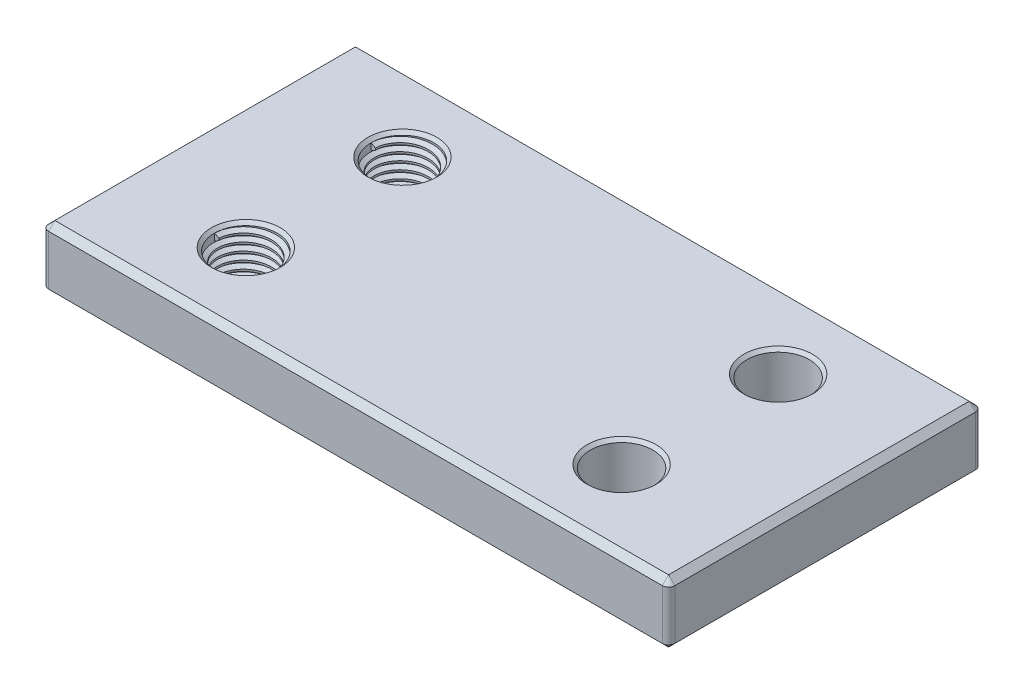
SolidWorks part; units mm, degrees
ref_plane "Alzado" through (0, 0, 0) normal (0, 0, 1) x (1, 0, 0)
ref_plane "Planta" through (0, 0, 0) normal (0, 1, 0) x (1, 0, 0)
ref_plane "Vista lateral" through (0, 0, 0) normal (1, 0, 0) x (0, 0, -1)
sketch "Croquis1" plane through (0, 0, 0) normal (0, 1, 0) x (1, 0, 0)
  line L0 (0, -1) -> (0, -49)
  line L1 (-1, -50) -> (-99, -50)
  line L2 (-100, -49) -> (-100, -1)
  line L3 (-99, 0) -> (-1, 0)
  arc A0 (0, -1) -> (-1, 0) centre (-1, -1) ccw
  arc A1 (0, -49) -> (-1, -50) centre (-1, -49) cw
  arc A2 (-99, -50) -> (-100, -49) centre (-99, -49) cw
  arc A3 (-100, -1) -> (-99, 0) centre (-99, -1) cw
  point P7 (0, 0)
  point P10 (0, -50)
  point P13 (-100, -50)
  dimension "D3" = 1
  dimension "D1" = 50
  dimension "D2" = 100
extrude "Saliente-Extruir1" add sketch "Croquis1" along normal blind 10
chamfer "Chaflán1" distance 1 angle 45 16 edges at (-0.2929, 0, 49.7071) (-50, 0, 50) (-99.7071, 0, 49.7071) (-100, 0, 25) (-99.7071, 0, 0.2929) (-50, 0, 0) (-0.2929, 0, 0.2929) (0, 0, 25) (-0.2929, 10, 49.7071) (0, 10, 25) (-0.2929, 10, 0.2929) (-50, 10, 0) (-99.7071, 10, 0.2929) (-100, 10, 25) (-99.7071, 10, 49.7071) (-50, 10, 50)
sketch "Croquis2" plane through (0, 10, 0) normal (0, 1, 0) x (1, 0, 0)
  line L0 (-100, -49) -> (-100, -1) construction
  line L1 (-99, 0) -> (-1, 0) construction
  circle A0 centre (-80, -12.5) radius 5
  circle A1 centre (-80, -37.5) radius 5
  point P0 (-80, -37.5)
  point P1 (-80, -12.5)
  dimension "D4" = 10
  dimension "D1" = 20
  dimension "D2" = 25
  dimension "D3" = 12.5
extrude "Cortar-Extruir1" cut sketch "Croquis2" against normal blind 10
chamfer "Chaflán2" distance 0.5 angle 45 2 edges at (-80, 10, 42.5) (-80, 10, 17.5)
thread "Rosca1" pitch 1.25 method extrude profile "Perfil de rosca2" start angle 0, offset 0, length 10, pitch 1.25, diameter 10
ref_plane "Plano2" through (-85, 9.5, 37.5) normal (0, 0, 1) x (-1, 0, 0)
sketch "Perfil de rosca2" plane through (-85, 9.5, 37.5) normal (0, 0, 1) x (-1, 0, 0)
  line L0 (0, 0) -> (0, 1.25) construction
  line L11 (0, 0) -> (0, 1.0937)
  line L12 (0, 1.0937) -> (-0.6766, 0.7031)
  line L13 (-0.6766, 0.7031) -> (-0.6766, 0.3906)
  line L15 (-0.6766, 0.3906) -> (0, 0)
  line L17 (-0.6766, 0.5469) -> (0, 0.5469) construction
  point P2 (0, 0)
  dimension "Pitch" = 1.25
  dimension "Profile_Angle" = 60
  dimension "Profile_Land" = 0.3125
  dimension "Profile_Height" = 0.6766
thread "Rosca2" pitch 1.25 method extrude profile "Perfil de rosca3" start angle 0, offset 0, length 0, pitch 1.25, diameter 10
ref_plane "Plano3" through (-85, 9.5, 12.5) normal (0, 0, 1) x (-1, 0, 0)
sketch "Perfil de rosca3" plane through (-85, 9.5, 12.5) normal (0, 0, 1) x (-1, 0, 0)
  line L0 (0, 0) -> (0, 1.25) construction
  line L11 (0, 0) -> (0, 1.0937)
  line L12 (0, 1.0937) -> (-0.6766, 0.7031)
  line L13 (-0.6766, 0.7031) -> (-0.6766, 0.3906)
  line L15 (-0.6766, 0.3906) -> (0, 0)
  line L17 (-0.6766, 0.5469) -> (0, 0.5469) construction
  point P2 (0, 0)
  dimension "Pitch" = 1.25
  dimension "Profile_Angle" = 60
  dimension "Profile_Land" = 0.3125
  dimension "Profile_Height" = 0.6766
sketch "Croquis11" plane through (0, 0, 0) normal (1, 0, 0) x (0, 0, -1)
  line L0 (-49, 0) -> (-49, -2.5875)
  line L1 (-49, -2.5875) -> (-1, -2.5875)
  line L2 (-1, -2.5875) -> (-1, 0)
  line L3 (-1, 0) -> (-49, 0)
extrude "Cortar-Extruir2" cut sketch "Croquis11" against normal through all
sketch "Croquis12" plane through (0, 10, 0) normal (0, 1, 0) x (1, 0, 0)
  line L0 (-1, -50) -> (-99, -50) construction
  line L1 (0, -1) -> (0, -49) construction
  circle A0 centre (-20, -12.5) radius 5
  circle A1 centre (-20, -37.5) radius 5
  point P4 (0, 0)
  point P5 (0, 0)
  dimension "D1" = 10
  dimension "D2" = 25
  dimension "D3" = 12.5
  dimension "D4" = 20
extrude "Cortar-Extruir3" cut sketch "Croquis12" against normal through all
chamfer "Chaflán3" distance 0.5 angle 45 2 edges at (-20, 10, 17.5) (-20, 10, 42.5)
